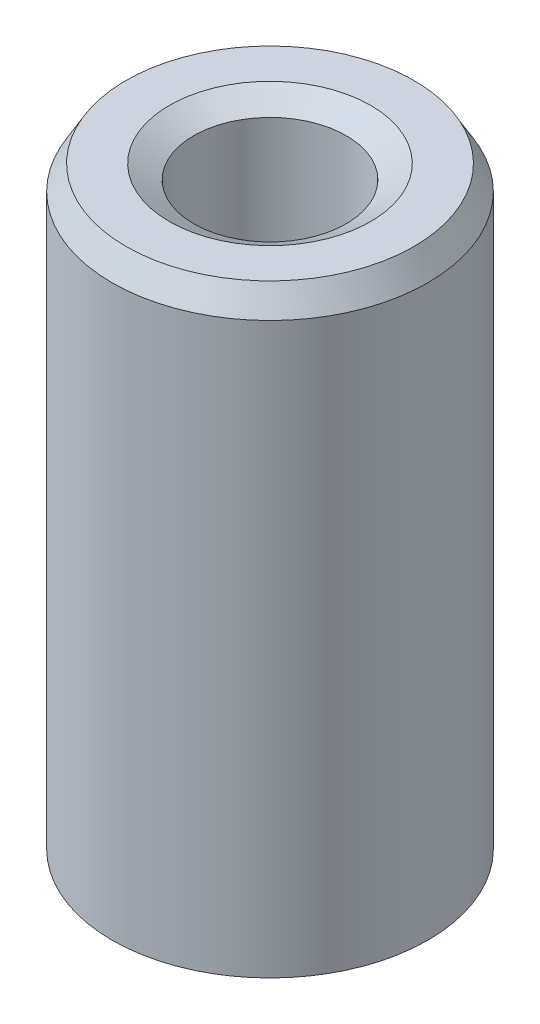
SolidWorks part; units mm, degrees
ref_plane "Front Plane" through (0, 0, 0) normal (0, 0, 1) x (1, 0, 0)
ref_plane "Top Plane" through (0, 0, 0) normal (0, 1, 0) x (1, 0, 0)
ref_plane "Right Plane" through (0, 0, 0) normal (1, 0, 0) x (0, 0, -1)
sketch "Sketch1" plane through (0, 0, 0) normal (0, 1, 0) x (1, 0, 0)
  circle A0 centre (0, 0) radius 20
  dimension "SLEEVE_OD" = 40
extrude "Boss-Extrude1" add sketch "Sketch1" along normal blind 76.9648
sketch "Sketch2" plane through (0, 0, 0) normal (0, 1, 0) x (1, 0, 0)
  circle A0 centre (0, 0) radius 9.6631
  dimension "BORE_D" = 19.3262
extrude "Cut-Extrude1" cut sketch "Sketch2" along normal through all
chamfer "Chamfer1" distance 3.0835 angle 30 4 edges at (0, 76.9648, 9.6631) (0, 0, 9.6631) (0, 0, 20) (0, 76.9648, 20) first distance on face at (0, 76.9648, 9.6631) first distance on face at (0, 0, 9.6631) first distance on face at (0, 76.9648, 20)
